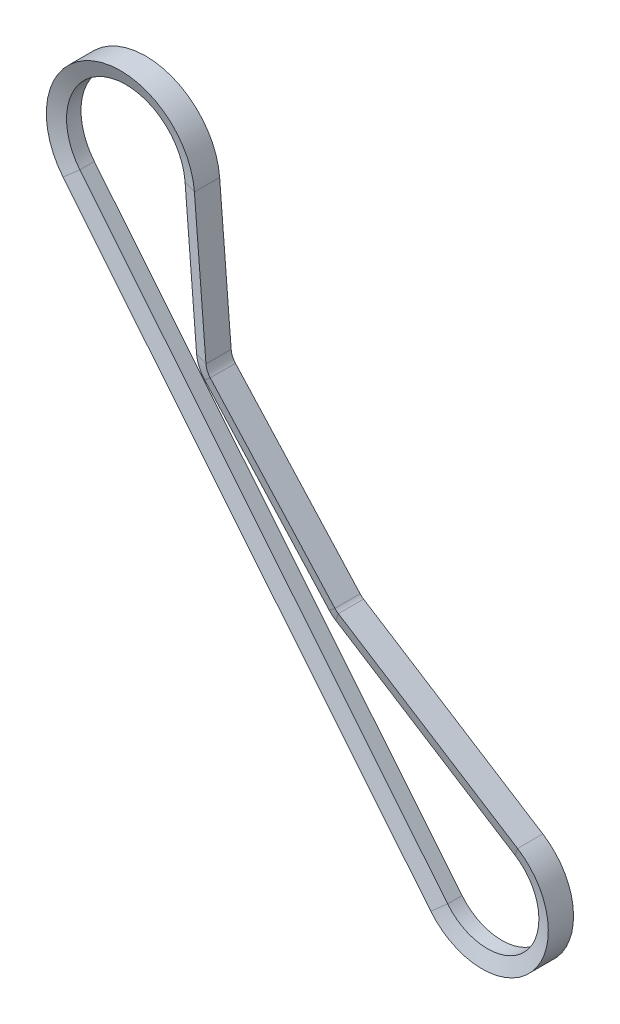
SolidWorks part; units mm, degrees
ref_plane "Front Plane" through (0, 0, 0) normal (0, 0, 1) x (1, 0, 0)
ref_plane "Top Plane" through (0, 0, 0) normal (0, 1, 0) x (1, 0, 0)
ref_plane "Right Plane" through (0, 0, 0) normal (1, 0, 0) x (0, 0, -1)
sketch "Sketch2" plane through (0, 0, 0) normal (0, 0, 1) x (1, 0, 0)
  line L0 (0, 0) -> (1, 0) construction
  line L1 (0, 0) -> (0, 1) construction
  line L12 (-19.3899, -15.7808) -> (-158.2479, 154.8341)
  line L14 (-108.6215, 174.7543) -> (-104.2733, 120.7148)
  line L15 (-102.6443, 116.9548) -> (-55.5811, 65.1373)
  line L16 (-54.2823, 64.0446) -> (13.3927, 21.1101)
  arc A4 (-158.2479, 154.8341) -> (-108.6215, 174.7543) centre (-136.5313, 172.5086) cw
  arc A7 (13.3927, 21.1101) -> (-19.3899, -15.7808) centre (0, 0) cw
  arc A8 (-104.2733, 120.7148) -> (-102.6443, 116.9548) centre (-97.9438, 121.2241) ccw
  arc A9 (-55.5811, 65.1373) -> (-54.2823, 64.0446) centre (-50.8805, 69.4066) ccw
ref_plane "Plane4" through (13.3927, 21.1101, 0) normal (0.8444, -0.5357, 0) x (-0.5357, -0.8444, 0)
sketch "Sketch3" plane through (13.3927, 21.1101, 0) normal (0.8444, -0.5357, 0) x (-0.5357, -0.8444, 0)
  line L0 (0, -4.7625) -> (0, 4.7625)
  line L1 (0, -4.7625) -> (5.588, -2.7286)
  line L2 (5.588, -2.7286) -> (5.588, 2.7286)
  line L3 (5.588, 2.7286) -> (0, 4.7625)
  line L4 (0, 0) -> (5.588, 0) construction
  dimension "D1" = 9.525
  dimension "D2" = 5.588
  dimension "D3" = 40
sweep "Sweep1" add profiles "Sketch3" path "Sketch2"
